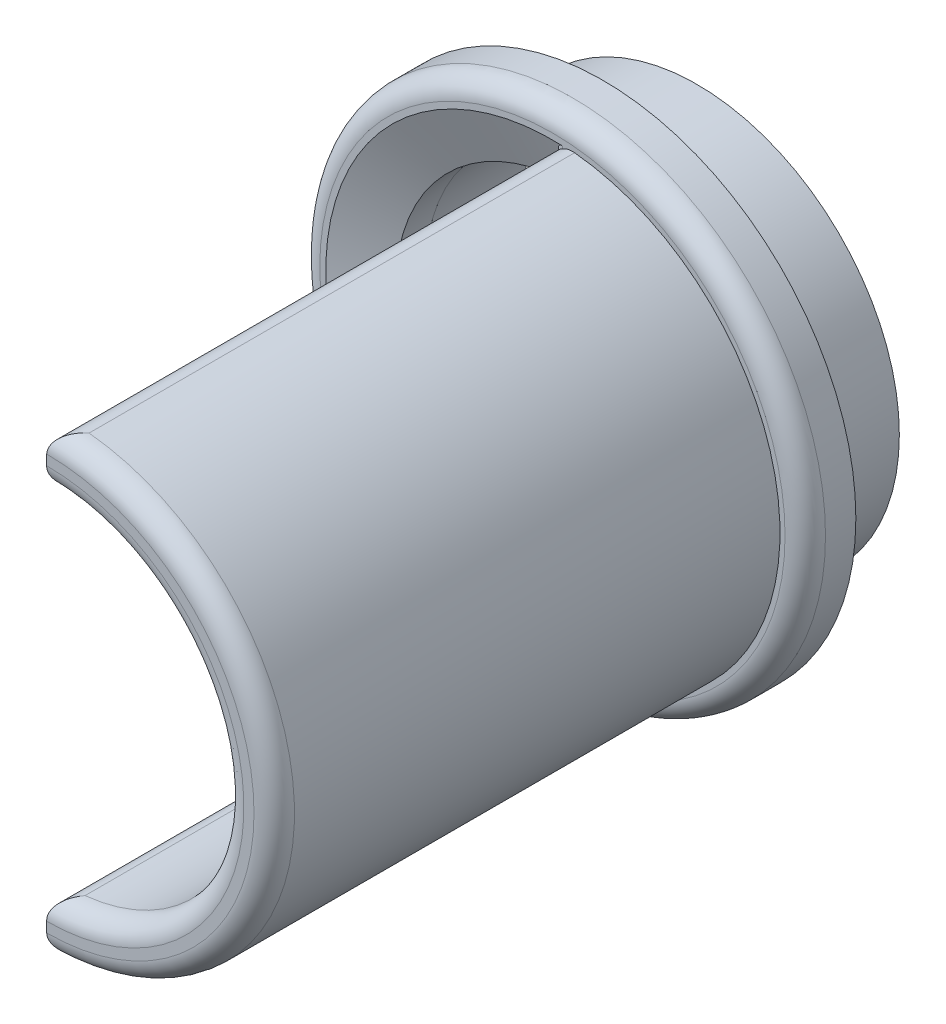
SolidWorks part; units mm, degrees
ref_plane "Front Plane" through (0, 0, 0) normal (0, 0, 1) x (1, 0, 0)
ref_plane "Top Plane" through (0, 0, 0) normal (0, 1, 0) x (1, 0, 0)
ref_plane "Right Plane" through (0, 0, 0) normal (1, 0, 0) x (0, 0, -1)
sketch "Sketch1" plane through (0, 0, 0) normal (0, 0, 1) x (1, 0, 0)
  circle A0 centre (0, 0) radius 20
  circle A1 centre (0, 0) radius 17.5
  dimension "D1" = 40
  dimension "D2" = 35
extrude "Boss-Extrude1" add sketch "Sketch1" along normal blind 9.3
sketch "Sketch2" plane through (0, 0, 9.3) normal (0, 0, 1) x (1, 0, 0)
  circle A2 centre (0, 0) radius 25
  circle A3 centre (0, 0) radius 17.5 construction
  circle A4 centre (0, 0) radius 17.5
  circle M1 centre (0, 0) radius 20
  circle M2 centre (0, 0) radius 17.5
  dimension "D1" = 50
extrude "Boss-Extrude2" add sketch "Sketch2" along normal blind 5 separate body contours M1 M2 | A2 M1
sketch "Sketch3" plane through (0, 0, 14.3) normal (0, 0, 1) x (1, 0, 0)
  line L0 (0, 22.5) -> (0, 17.5)
  line L1 (0, -17.5) -> (0, -22.5)
  arc A0 (0, 17.5) -> (0, -17.5) centre (0, 0) cw
  circle A1 centre (0, 0) radius 17.5 construction
  arc A2 (0, 22.5) -> (0, -22.5) centre (0, 0) cw
  dimension "D1" = 5
extrude "Boss-Extrude3" add sketch "Sketch3" along normal blind 50
fillet "Fillet1" radius 2 7 edges at (25, 0, 14.3) (22.5, 0, 64.3) (17.5, 0, 64.3) (0, 17.5, 39.3) (0, -17.5, 39.3) (0, -22.5, 39.3) (0, 22.5, 39.3)
sketch "Sketch4" plane through (0, 0, 0) normal (1, 0, 0) x (0, 0, -1)
  line L0 (-14.3, -17.5) -> (-9.3, -17.5) construction
  line L1 (-12.3, -25) -> (-12.3, 25) construction
  line L2 (-14.3, -22.4022) -> (-12.3, -17.5)
  line L3 (-12.3, -17.5) -> (-14.3, -17.5)
  line L4 (-14.3, -17.5) -> (-14.3, -22.4022)
  line L5 (0, 0) -> (-62.3, 0)
  line L6 (-62.3, -17.4077) -> (-62.3, 17.4077) construction
  point P0 (-12.3, -17.5)
revolve "Cut-Revolve1" cut sketch "Sketch4" angle 180 about L5
fillet "Fillet2" radius 1 2 edges at (0, 17.5, 13.3) (0, 18.4486, 14.3)
